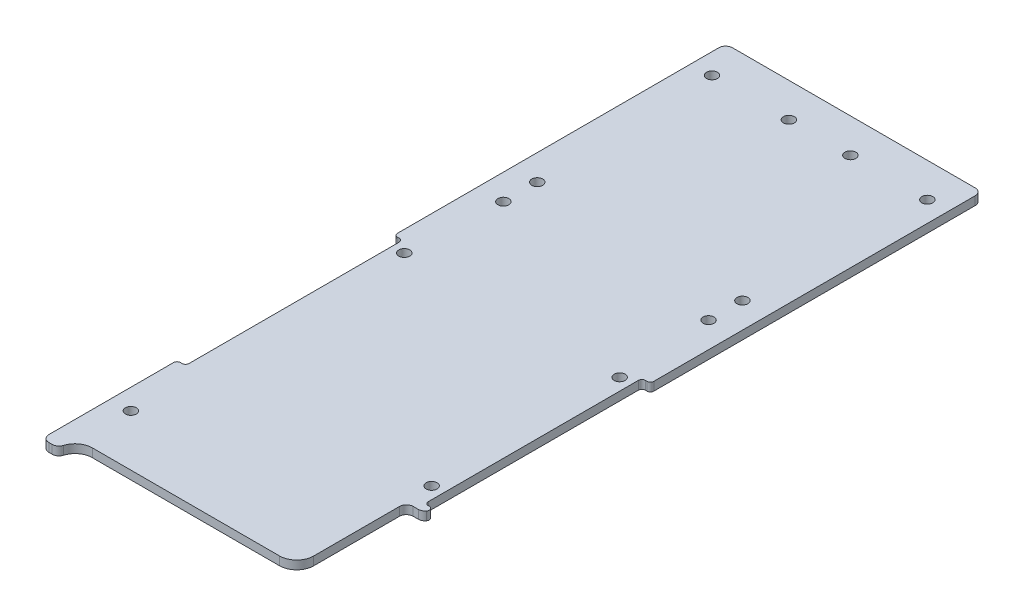
SolidWorks part; units mm, degrees
ref_plane "Front Plane" through (0, 0, 0) normal (0, 0, 1) x (1, 0, 0)
ref_plane "Top Plane" through (0, 0, 0) normal (0, 1, 0) x (1, 0, 0)
ref_plane "Right Plane" through (0, 0, 0) normal (1, 0, 0) x (0, 0, -1)
sketch "Sketch1" plane through (0, 0, 0) normal (0, 1, 0) x (1, 0, 0)
  line L0 (-39.9997, 0) -> (-39.9997, 114.3) construction
  line L1 (-47.625, 127) -> (47.625, 127)
  line L2 (-47.625, 127) -> (-47.625, -127)
  line L3 (-47.625, -127) -> (47.625, -127)
  line L4 (47.625, 127) -> (47.625, -127)
  line L5 (-47.625, 127) -> (47.625, -127) construction
  line L6 (-47.625, -127) -> (47.625, 127) construction
  line L7 (0, 0) -> (0, 127) construction
  line L8 (-39.9997, 0) -> (-39.9997, -101.6) construction
  line L9 (-39.9997, 0) -> (0, 0) construction
  line L10 (-41.275, -127) -> (-41.275, -120.65)
  line L11 (-41.275, -120.65) -> (41.275, -120.65)
  line L12 (41.275, -120.65) -> (41.275, -127)
  line L13 (-39.9997, 114.3) -> (-11.4247, 114.3) construction
  line L14 (39.9997, 114.3) -> (11.4247, 114.3) construction
  circle A0 centre (-39.9997, 114.3) radius 2.032
  circle A1 centre (-39.9997, 0) radius 2.032
  circle A2 centre (-39.9997, -101.6) radius 2.032
  circle A3 centre (39.9997, -101.6) radius 2.032
  circle A4 centre (39.9997, 0) radius 2.032
  circle A5 centre (39.9997, 114.3) radius 2.032
  circle A6 centre (-11.4247, 114.3) radius 2.032
  circle A7 centre (11.4247, 114.3) radius 2.032
  circle A8 centre (-39.9997, -69.85) radius 2.032
  circle A9 centre (39.9997, -69.85) radius 2.032
  point P0 (0, 0)
  dimension "D4" = 4.064
  dimension "D10" = 28.575
  dimension "D1" = 95.25
  dimension "D2" = 254
  dimension "D3" = 7.6253
  dimension "D5" = 12.7
  dimension "D6" = 25.4
  dimension "D7" = 6.35
  dimension "D8" = 6.35
  dimension "D9" = 6.35
  dimension "D11" = 69.85
extrude "Boss-Extrude1" add sketch "Sketch1" along normal blind 3.175 contours L4 L1 L2 L3 A4 A0 A1 A2 A3 A5 | A8 | A3 region at (0, 0, -2.6944) region at (39.9997, 0, 101.6) region at (-39.9997, 0, 69.85)
fillet "Fillet1" radius 2.54 4 edges at (-47.625, 1.5875, -127) (47.625, 1.5875, -127) (47.625, 1.5875, 127) (-47.625, 1.5875, 127)
fillet "Fillet2" radius 2.54 2 edges at (41.275, 1.5875, 127) (-41.275, 1.5875, 127)
fillet "Fillet3" radius 6.35 2 edges at (41.275, 1.5875, 120.65) (-41.275, 1.5875, 120.65)
sketch "Sketch2" plane through (0, 0, 0) normal (0, -1, 0) x (1, 0, 0)
  line L1 (43.815, 127) -> (45.085, 127) construction
  line L2 (40.6451, 123.5787) -> (40.6451, 79.8881)
  line L3 (40.6451, 79.8881) -> (47.625, 79.8881)
  line L11 (47.625, -124.46) -> (47.625, 124.46) construction
  line L12 (43.815, 127) -> (45.085, 127)
  line L13 (47.625, 79.8881) -> (47.625, 124.46)
  arc A0 (35.2956, 120.65) -> (41.3809, 125.1857) centre (35.2956, 127) ccw construction
  arc A1 (43.815, 127) -> (41.3809, 125.1857) centre (43.815, 124.46) ccw construction
  arc A2 (47.625, 124.46) -> (45.085, 127) centre (45.085, 124.46) ccw construction
  arc A3 (40.6451, 123.5787) -> (41.3809, 125.1857) centre (35.2956, 127) ccw
  arc A4 (43.815, 127) -> (41.3809, 125.1857) centre (43.815, 124.46) ccw
  arc A5 (47.625, 124.46) -> (45.085, 127) centre (45.085, 124.46) ccw
  dimension "D2" = 47.1119
  dimension "D1" = 6.9799
extrude "Cut-Extrude1" cut sketch "Sketch2" against normal through all
fillet "Fillet4" radius 6.35 1 edges at (40.6451, 1.5875, 123.5787)
fillet "Fillet5" radius 2.54 2 edges at (47.625, 1.5875, 79.8881) (40.6451, 1.5875, 79.8881)
sketch "Sketch3" plane through (0, 0, 0) normal (0, -1, 0) x (1, 0, 0)
  line L0 (-36.3051, -49.7791) -> (-39.9119, -49.7791) construction
  line L1 (-40.4199, -49.276) -> (-40.4199, -45.7043) construction
  line L2 (-35.7971, -45.7043) -> (-35.7971, -49.276) construction
  line L3 (-39.9119, -45.2013) -> (-36.3051, -45.2013) construction
  line L4 (-36.3051, -37.2027) -> (-39.9119, -37.2027) construction
  line L5 (-35.7971, -33.1279) -> (-35.7971, -36.6996) construction
  line L6 (-40.4199, -36.6996) -> (-40.4199, -33.1279) construction
  line L7 (-39.9119, -32.6249) -> (-36.3051, -32.6249) construction
  line L8 (36.2881, -32.6249) -> (39.8949, -32.6249) construction
  line L9 (40.4029, -33.1279) -> (40.4029, -36.6996) construction
  line L10 (39.8949, -37.2027) -> (36.2881, -37.2027) construction
  line L11 (35.7801, -36.6996) -> (35.7801, -33.1279) construction
  line L12 (36.2881, -45.2013) -> (39.8949, -45.2013) construction
  line L13 (35.7801, -49.276) -> (35.7801, -45.7043) construction
  line L14 (40.4029, -45.7043) -> (40.4029, -49.276) construction
  line L15 (39.8949, -49.7791) -> (36.2881, -49.7791) construction
  line L16 (-36.3051, -49.7791) -> (-39.9119, -49.7791)
  line L17 (-40.4199, -49.276) -> (-40.4199, -45.7043)
  line L18 (-35.7971, -45.7043) -> (-35.7971, -49.276)
  line L19 (-39.9119, -45.2013) -> (-36.3051, -45.2013)
  line L20 (-36.3051, -37.2027) -> (-39.9119, -37.2027)
  line L21 (-35.7971, -33.1279) -> (-35.7971, -36.6996)
  line L22 (-40.4199, -36.6996) -> (-40.4199, -33.1279)
  line L23 (-39.9119, -32.6249) -> (-36.3051, -32.6249)
  line L24 (36.2881, -32.6249) -> (39.8949, -32.6249)
  line L25 (40.4029, -33.1279) -> (40.4029, -36.6996)
  line L26 (39.8949, -37.2027) -> (36.2881, -37.2027)
  line L27 (35.7801, -36.6996) -> (35.7801, -33.1279)
  line L28 (36.2881, -45.2013) -> (39.8949, -45.2013)
  line L29 (35.7801, -49.276) -> (35.7801, -45.7043)
  line L30 (40.4029, -45.7043) -> (40.4029, -49.276)
  line L31 (39.8949, -49.7791) -> (36.2881, -49.7791)
  line L32 (-47.625, -25.836) -> (47.625, -25.836)
  line L33 (-47.625, -124.46) -> (-47.625, 124.46) construction
  line L34 (47.625, -124.46) -> (47.625, 77.3481) construction
  line L35 (0, -25.836) -> (0, -56.0686) construction
  line L1362 (-40.4199, -34.9138) -> (-35.7971, -34.9138)
  line L1857 (-38.1085, -32.6249) -> (-38.1085, -37.2027)
  line L1858 (-38.1085, -45.2013) -> (-38.1085, -49.7791)
  line L1859 (-40.4199, -47.4902) -> (-35.7971, -47.4902)
  circle A0 centre (-38.1085, -34.9138) radius 2.032
  circle A1 centre (-38.1085, -47.4902) radius 2.032
  circle A2 centre (38.1085, -47.4902) radius 2.032
  circle A3 centre (38.1085, -34.9138) radius 2.032
  ellipse E0 centre (-39.9119, -45.7043) end of major axis (-39.4039, -45.7043) minor radius 0.5031 (-39.9119, -45.2013) -> (-40.4199, -45.7043) ccw construction
  ellipse E1 centre (-39.9119, -49.276) end of major axis (-39.4039, -49.276) minor radius 0.5031 (-40.4199, -49.276) -> (-39.9119, -49.7791) ccw construction
  ellipse E6 centre (-36.3051, -49.276) end of major axis (-35.7971, -49.276) minor radius 0.5031 (-36.3051, -49.7791) -> (-35.7971, -49.276) ccw construction
  ellipse E7 centre (-36.3051, -45.7043) end of major axis (-35.7971, -45.7043) minor radius 0.5031 (-35.7971, -45.7043) -> (-36.3051, -45.2013) ccw construction
  ellipse E8 centre (-39.9119, -36.6996) end of major axis (-39.4039, -36.6996) minor radius 0.5031 (-40.4199, -36.6996) -> (-39.9119, -37.2027) ccw construction
  ellipse E9 centre (-36.3051, -36.6996) end of major axis (-35.7971, -36.6996) minor radius 0.5031 (-36.3051, -37.2027) -> (-35.7971, -36.6996) ccw construction
  ellipse E10 centre (-36.3051, -33.1279) end of major axis (-35.7971, -33.1279) minor radius 0.5031 (-35.7971, -33.1279) -> (-36.3051, -32.6249) ccw construction
  ellipse E11 centre (-39.9119, -33.1279) end of major axis (-39.4039, -33.1279) minor radius 0.5031 (-39.9119, -32.6249) -> (-40.4199, -33.1279) ccw construction
  ellipse E12 centre (39.8949, -33.1279) end of major axis (40.4029, -33.1279) minor radius 0.5031 (40.4029, -33.1279) -> (39.8949, -32.6249) ccw construction
  ellipse E13 centre (36.2881, -33.1279) end of major axis (36.7961, -33.1279) minor radius 0.5031 (36.2881, -32.6249) -> (35.7801, -33.1279) ccw construction
  ellipse E14 centre (39.8949, -36.6996) end of major axis (40.4029, -36.6996) minor radius 0.5031 (39.8949, -37.2027) -> (40.4029, -36.6996) ccw construction
  ellipse E15 centre (36.2881, -36.6996) end of major axis (36.7961, -36.6996) minor radius 0.5031 (35.7801, -36.6996) -> (36.2881, -37.2027) ccw construction
  ellipse E16 centre (36.2881, -45.7043) end of major axis (36.7961, -45.7043) minor radius 0.5031 (36.2881, -45.2013) -> (35.7801, -45.7043) ccw construction
  ellipse E17 centre (36.2881, -49.276) end of major axis (36.7961, -49.276) minor radius 0.5031 (35.7801, -49.276) -> (36.2881, -49.7791) ccw construction
  ellipse E18 centre (39.8949, -45.7043) end of major axis (40.4029, -45.7043) minor radius 0.5031 (40.4029, -45.7043) -> (39.8949, -45.2013) ccw construction
  ellipse E19 centre (39.8949, -49.276) end of major axis (40.4029, -49.276) minor radius 0.5031 (39.8949, -49.7791) -> (40.4029, -49.276) ccw construction
  ellipse E20 centre (-39.9119, -45.7043) end of major axis (-39.4039, -45.7043) minor radius 0.5031 (-39.9119, -45.2013) -> (-40.4199, -45.7043) ccw
  ellipse E21 centre (-39.9119, -49.276) end of major axis (-39.4039, -49.276) minor radius 0.5031 (-40.4199, -49.276) -> (-39.9119, -49.7791) ccw
  ellipse E22 centre (-36.3051, -49.276) end of major axis (-35.7971, -49.276) minor radius 0.5031 (-36.3051, -49.7791) -> (-35.7971, -49.276) ccw
  ellipse E23 centre (-36.3051, -45.7043) end of major axis (-35.7971, -45.7043) minor radius 0.5031 (-35.7971, -45.7043) -> (-36.3051, -45.2013) ccw
  ellipse E24 centre (-39.9119, -36.6996) end of major axis (-39.4039, -36.6996) minor radius 0.5031 (-40.4199, -36.6996) -> (-39.9119, -37.2027) ccw
  ellipse E25 centre (-36.3051, -36.6996) end of major axis (-35.7971, -36.6996) minor radius 0.5031 (-36.3051, -37.2027) -> (-35.7971, -36.6996) ccw
  ellipse E26 centre (-36.3051, -33.1279) end of major axis (-35.7971, -33.1279) minor radius 0.5031 (-35.7971, -33.1279) -> (-36.3051, -32.6249) ccw
  ellipse E27 centre (-39.9119, -33.1279) end of major axis (-39.4039, -33.1279) minor radius 0.5031 (-39.9119, -32.6249) -> (-40.4199, -33.1279) ccw
  ellipse E28 centre (39.8949, -33.1279) end of major axis (40.4029, -33.1279) minor radius 0.5031 (40.4029, -33.1279) -> (39.8949, -32.6249) ccw
  ellipse E29 centre (36.2881, -33.1279) end of major axis (36.7961, -33.1279) minor radius 0.5031 (36.2881, -32.6249) -> (35.7801, -33.1279) ccw
  ellipse E30 centre (39.8949, -36.6996) end of major axis (40.4029, -36.6996) minor radius 0.5031 (39.8949, -37.2027) -> (40.4029, -36.6996) ccw
  ellipse E31 centre (36.2881, -36.6996) end of major axis (36.7961, -36.6996) minor radius 0.5031 (35.7801, -36.6996) -> (36.2881, -37.2027) ccw
  ellipse E32 centre (36.2881, -45.7043) end of major axis (36.7961, -45.7043) minor radius 0.5031 (36.2881, -45.2013) -> (35.7801, -45.7043) ccw
  ellipse E33 centre (36.2881, -49.276) end of major axis (36.7961, -49.276) minor radius 0.5031 (35.7801, -49.276) -> (36.2881, -49.7791) ccw
  ellipse E34 centre (39.8949, -45.7043) end of major axis (40.4029, -45.7043) minor radius 0.5031 (40.4029, -45.7043) -> (39.8949, -45.2013) ccw
  ellipse E35 centre (39.8949, -49.276) end of major axis (40.4029, -49.276) minor radius 0.5031 (39.8949, -49.7791) -> (40.4029, -49.276) ccw
  dimension "D2" = 4.064
extrude "Cut-Extrude2" cut sketch "Sketch3" against normal through all contours A0 | A1 | A2 | A3
sketch "Sketch4" plane through (0, 3.175, 0) normal (0, 1, 0) x (1, 0, 0)
  line L11 (-47.625, 124.46) -> (-47.625, -124.46) construction
  line L12 (-47.625, -76.835) -> (-44.45, -76.835)
  line L13 (-47.625, -76.835) -> (-47.625, 3.81)
  line L15 (-47.625, 3.81) -> (-44.45, 3.81)
  line L16 (-44.45, -76.835) -> (-44.45, 3.81)
  line L17 (47.625, 124.46) -> (47.625, -77.3481) construction
  line L18 (47.625, -76.835) -> (44.45, -76.835)
  line L19 (47.625, -76.835) -> (47.625, 3.81)
  line L20 (47.625, 3.81) -> (44.45, 3.81)
  line L45 (44.45, -76.835) -> (44.45, 3.81)
  line L47 (43.1851, -79.8881) -> (45.085, -79.8881) construction
  dimension "D1" = 3.175
  dimension "D2" = 80.645
  dimension "D3" = 3.0531
extrude "Cut-Extrude3" cut sketch "Sketch4" against normal through all and the other way through all
fillet "Fillet6" radius 1.27 8 edges at (-44.45, 1.5875, -3.81) (-47.625, 1.5875, -3.81) (-47.625, 1.5875, 76.835) (-44.45, 1.5875, 76.835) (44.45, 1.5875, 76.835) (47.625, 1.5875, 76.835) (44.45, 1.5875, -3.81) (47.625, 1.5875, -3.81)
